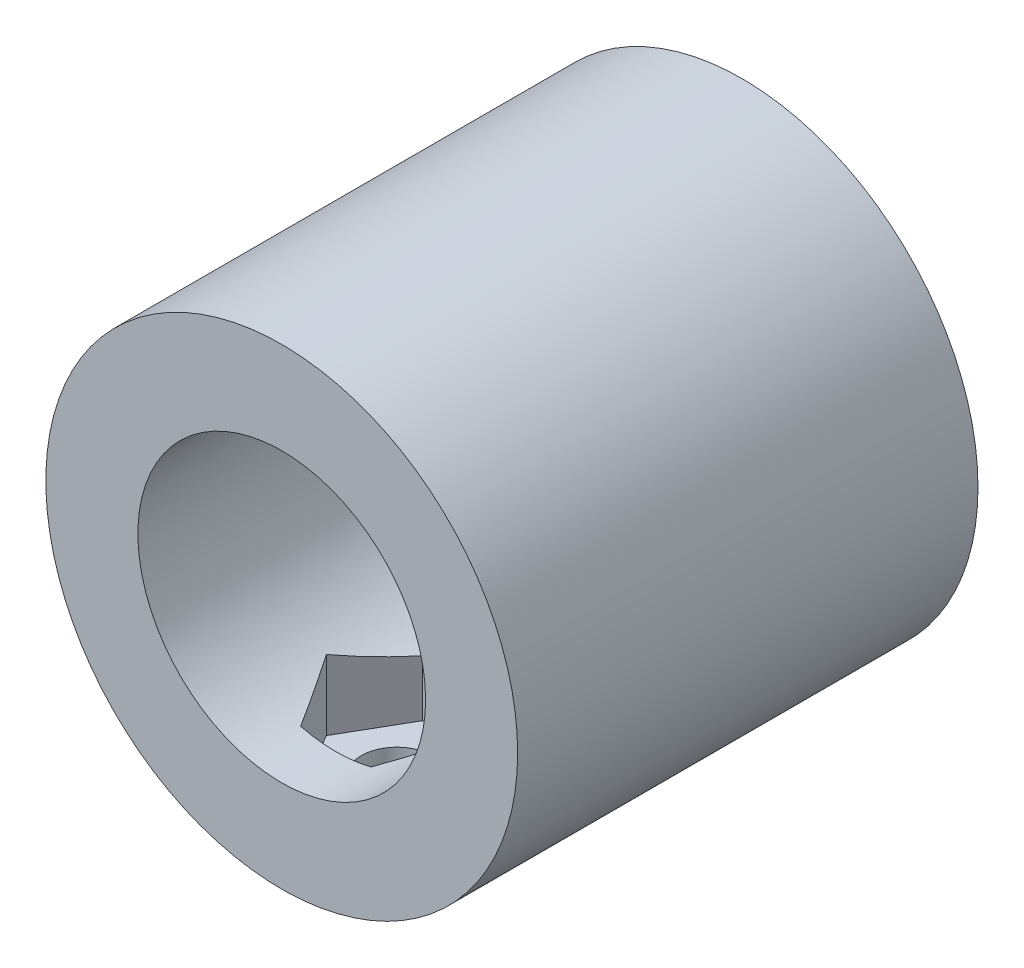
SolidWorks part; units mm, degrees
ref_plane "Alzado" through (0, 0, 0) normal (0, 0, 1) x (1, 0, 0)
ref_plane "Planta" through (0, 0, 0) normal (0, 1, 0) x (1, 0, 0)
ref_plane "Vista lateral" through (0, 0, 0) normal (1, 0, 0) x (0, 0, -1)
sketch "Croquis1" plane through (0, 0, 0) normal (0, 0, 1) x (1, 0, 0)
  circle A0 centre (0, 0) radius 6.25
  circle A1 centre (0, 0) radius 10.25
  dimension "D1" = 12.5
  dimension "D2" = 4
extrude "Saliente-Extruir1" add sketch "Croquis1" along normal blind 10 and the other way blind 10
sketch "Croquis2" plane through (0, 0, 0) normal (0, 1, 0) x (1, 0, 0)
  line L0 (-12.7223, 0) -> (13.2269, 0) construction
  line L1 (0, 9.8936) -> (0, -11.381) construction
  line L2 (1.53, -2.35) -> (-1.53, -2.35)
  line L3 (-1.53, -2.35) -> (-3.06, -5)
  line L4 (-3.06, -5) -> (-1.53, -7.65)
  line L5 (-1.53, -7.65) -> (1.53, -7.65)
  line L6 (1.53, -7.65) -> (3.06, -5)
  line L7 (3.06, -5) -> (1.53, -2.35)
  line L8 (3.06, 5) -> (1.53, 2.35)
  line L9 (1.53, 7.65) -> (3.06, 5)
  line L10 (-1.53, 7.65) -> (1.53, 7.65)
  line L11 (-3.06, 5) -> (-1.53, 7.65)
  line L12 (-1.53, 2.35) -> (-3.06, 5)
  line L13 (1.53, 2.35) -> (-1.53, 2.35)
  circle A0 centre (0, -5) radius 2.65 construction
  circle A1 centre (0, -5) radius 1.55
  circle A2 centre (0, 5) radius 1.55
  dimension "D3" = 3.1
  dimension "D1" = 5.3
  dimension "D2" = 5
extrude "Cortar-Extruir1" cut sketch "Croquis2" against normal blind 8.5
sketch "Croquis3" plane through (0, 0, 0) normal (0, 1, 0) x (1, 0, 0)
  circle A0 centre (0, 5) radius 1.55
  circle A1 centre (0, -5) radius 1.55
  dimension "D1" = 3.1
  dimension "D2" = 3.1
extrude "Cortar-Extruir2" cut sketch "Croquis3" against normal blind 28.5
